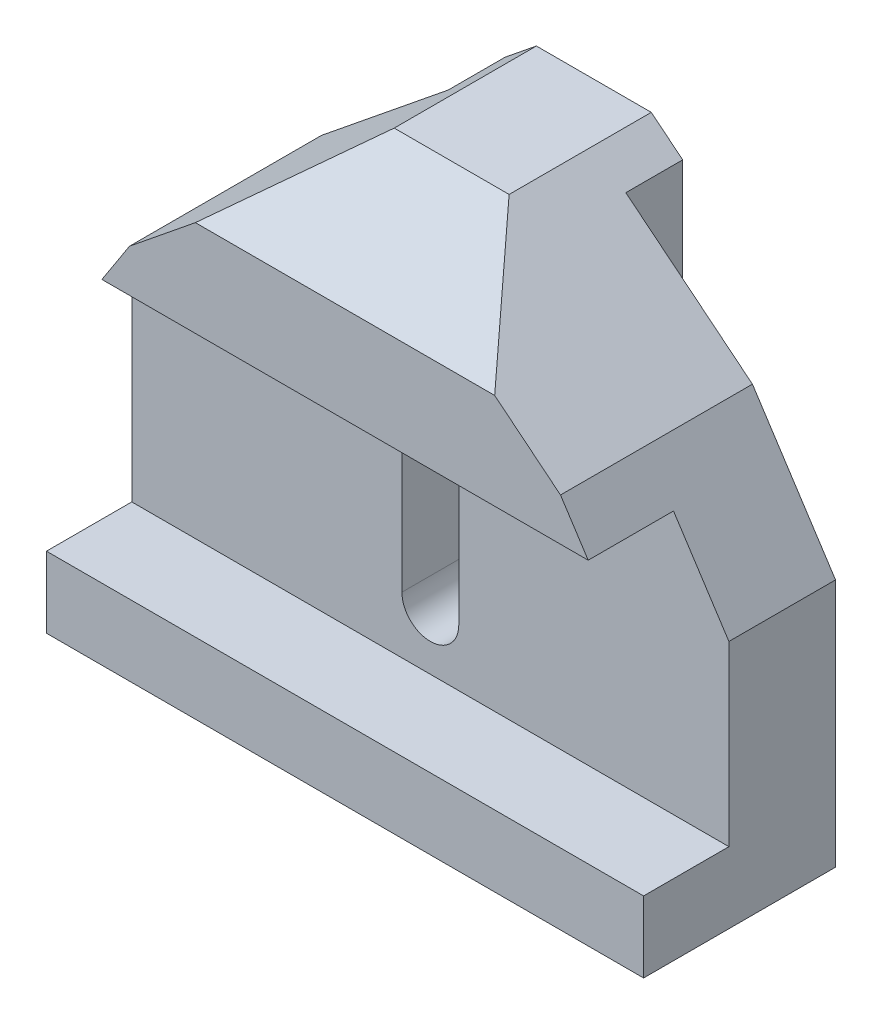
SolidWorks part; units mm, degrees
ref_plane "Front Plane" through (0, 0, 0) normal (0, 0, 1) x (1, 0, 0)
ref_plane "Top Plane" through (0, 0, 0) normal (0, 1, 0) x (1, 0, 0)
ref_plane "Right Plane" through (0, 0, 0) normal (1, 0, 0) x (0, 0, -1)
sketch "Sketch1" plane through (0, 0, 0) normal (1, 0, 0) x (0, 0, -1)
  line L0 (0, 0) -> (0, 71)
  line L1 (0, 71) -> (-35, 71)
  line L4 (-35, 47) -> (-23, 47)
  line L5 (-23, 47) -> (-23, 10)
  line L6 (-23, 10) -> (-35, 10)
  line L7 (-35, 10) -> (-35, 0)
  line L8 (-35, 0) -> (0, 0)
  line L9 (-35, 47) -> (-35, 71)
  line L10 (-8, 71) -> (-8, 0)
  point P3 (-35, 71)
  point P13 (0, 73.5463)
  point P14 (0, 61.3494)
  point P15 (0, 0)
  point P16 (-35, 70.5267)
  dimension "D1" = 35
  dimension "D2" = 12
  dimension "D3" = 37
  dimension "D6" = 8
  dimension "D7" = 71
  dimension "D8" = 10
extrude "Boss-Extrude1" add sketch "Sketch1" along normal mid plane 25 contours L1 L10 L8 L0 region at (0, 35.5, 4)
extrude "Boss-Extrude2" add sketch "Sketch1<3>" along normal mid plane 84 contours L10 L1 L9 L4 L5 L6 L7 L8 region at (0, 37.61, 19.2393)
sketch "Sketch1<3>" plane through (0, 0, 0) normal (1, 0, 0) x (0, 0, -1) same geometry as "Sketch1"
sketch "Sketch2" plane through (0, 0, 0) normal (0, 0, 1) x (1, 0, 0)
  line L0 (8.0825, 71) -> (30.3107, 53)
  line L1 (42, 71) -> (-42, 71) construction
  line L2 (30.3107, 53) -> (42, 35)
  line L3 (42, 47) -> (42, 10) construction
  line L4 (42, 35) -> (42, 0)
  line L5 (42, 0) -> (0, 0)
  line L6 (0, -1.6925) -> (0, 73.6371) construction
  line L7 (0, 39) -> (0, 18) construction
  line L8 (4, 39) -> (4, 18)
  line L9 (-4, 39) -> (-4, 18)
  line L10 (42, 0) -> (-42, 0) construction
  line L11 (8.0825, 71) -> (42, 71)
  line L12 (42, 71) -> (42, 35)
  line L13 (-42, 71) -> (-42, 35)
  line L14 (-8.0825, 71) -> (-42, 71)
  line L15 (-42, 35) -> (-42, 0)
  line L16 (-30.3107, 53) -> (-42, 35)
  line L17 (-8.0825, 71) -> (-30.3107, 53)
  arc A0 (4, 39) -> (-4, 39) centre (0, 39) ccw
  arc A1 (-4, 18) -> (4, 18) centre (0, 18) ccw
  point P15 (0, 28.5)
  dimension "D5" = 8
  dimension "D1" = 33
  dimension "D2" = 51
  dimension "D3" = 18
  dimension "D4" = 35
  dimension "D6" = 21
  dimension "D7" = 39
extrude "Cut-Extrude1" cut sketch "Sketch2" along normal up to next contours L12 L11 L0 L2 | L17 L14 L13 L16 | A0 L9 A1 L8 region at (31.4109, 60.1036, 0) region at (-31.4109, 60.1036, 0)
chamfer "Chamfer1" distance 15 angle 35 1 edges at (0, 71, 35) first distance on face at (0, 71, 17.5)
